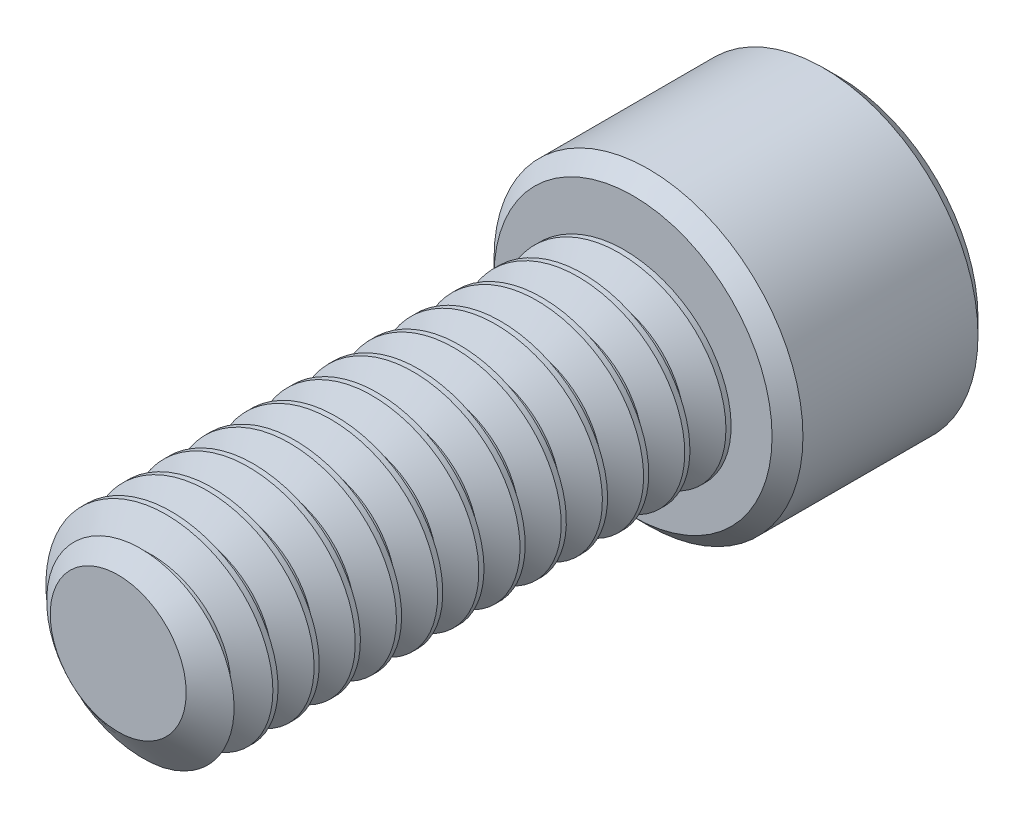
SolidWorks part; units mm, degrees
note: '?' marks a value the reader was unsure of.
other "DetailItem1"
ref_plane "Front Plane" through (0, 0, 0) normal (0, 0, 1) x (1, 0, 0)
ref_plane "Top Plane" through (0, 0, 0) normal (0, 1, 0) x (1, 0, 0)
ref_plane "Right Plane" through (0, 0, 0) normal (1, 0, 0) x (0, 0, -1)
sketch "Sketch1" plane through (0, 0, 0) normal (0, 0, 1) x (1, 0, 0)
  circle A0 centre (0, 0) radius 3.175
  dimension "OD" = 6.35
extrude "Extrude1" add sketch "Sketch1" against normal blind 15.875
sketch "Sketch2" plane through (0, 0, 0) normal (0, 0, 1) x (1, 0, 0)
  circle A0 centre (0, 0) radius 3.175 construction
  circle A1 centre (0, 0) radius 3.175
curve "Helix/Spiral1" pitch 1.27 height 17.145 turns 13.5 parameters "pitch"=1.27
sketch "Sketch3" plane through (0, 0, 0) normal (1, 0, 0) x (0, 0, -1)
  line L0 (-1.1112, 3.175) -> (-0.635, 2.3501)
  line L1 (-0.635, 2.3501) -> (-0.4762, 2.3501)
  line L2 (-0.4762, 2.3501) -> (0, 3.175)
  line L3 (-1.1112, 3.175) -> (0, 3.175)
  line L4 (-0.5556, 3.175) -> (-0.5556, 2.3501) construction
  line L5 (-0.8731, 2.7626) -> (-0.2381, 2.7626) construction
  line L6 (0, 3.175) -> (0, -3.175) construction
  dimension "D1" = 0.1588
  dimension "D2" = 0.635
  dimension "D3" = 60
sweep "Cut-Sweep1" cut profiles "Sketch3" path "Helix/Spiral1"
sketch "Sketch4" plane through (0, 0, 0) normal (1, 0, 0) x (0, 0, -1)
  line L0 (0.7554, 3.175) -> (0, 2.0961)
  line L1 (0, 2.0961) -> (0, 3.175)
  line L2 (0.7554, 3.175) -> (0, 3.175)
  line L3 (-1.1112, 3.175) -> (0, 3.175) construction
  line L4 (0, 0) -> (7.0209, 0) construction
  dimension "D1" = 55
  dimension "D2" = 0.254
revolve "Cut-Revolve1" cut sketch "Sketch4" angle 360 about L4
sketch "Sketch6" plane through (0, 0, -15.875) normal (0, 0, -1) x (-1, 0, 0)
  circle A0 centre (0, 0) radius 4.7625
  dimension "head dia" = 9.525
extrude "Extrude2" add sketch "Sketch6" along normal blind 6.35
sketch "Sketch7" plane through (0, 0, -22.225) normal (0, 0, -1) x (-1, 0, 0)
  line L1 (0, 2.7496) -> (-2.3812, 1.3748)
  line L2 (-2.3812, 1.3748) -> (-2.3813, -1.3748)
  line L3 (-2.3813, -1.3748) -> (0, -2.7496)
  line L4 (0, -2.7496) -> (2.3813, -1.3748)
  line L5 (2.3813, -1.3748) -> (2.3813, 1.3748)
  line L6 (2.3813, 1.3748) -> (0, 2.7496)
  circle A0 centre (0, 0) radius 2.3813 construction
  dimension "hex dia" = 4.7625
extrude "Cut-Extrude1" cut sketch "Sketch7" against normal blind 3.5719
sketch "Sketch8" plane through (0, 0, -22.225) normal (0, 0, -1) x (-1, 0, 0)
  circle A0 centre (0, 0) radius 2.7496
extrude "Cut-Extrude2" cut sketch "Sketch8" against normal through all draft 45
chamfer "Chamfer1" distance 0.4763 angle 45 2 edges at (-4.7625, 0, -22.225) (-4.7625, 0, -15.875)
sketch "Sketch10" plane through (0, 0, -15.875) normal (0, 0, 1) x (1, 0, 0)
  circle A1 centre (0, 0) radius 3.175
  circle A2 centre (0, 0) radius 3.175
  dimension "D1" = 0
ref_plane "Plane1" through (0, 0, -38.1) normal (0, 0, 1) x (1, 0, 0)
extrude "partial thread" [suppressed] add sketch "Sketch10" along normal up to surface (12.7 mm away) separate body
chamfer "Chamfer2" [suppressed] distance 0.127 angle 45
combine bodies "Combine1" [suppressed] operation type? add bodies to combine 107 108
sketch "Sketch9" plane through (0, 0, 0) normal (1, 0, 0) x (0, 0, -1)
  line L0 (0, 3.175) -> (0, -3.175) construction
  line L1 (3.175, 3.175) -> (3.175, -3.175) construction
  dimension "D1" = 3.175
equation "\"D3@Helix/Spiral1\" = \"screw length@Extrude1\"+\"pitch@Helix/Spiral1\""
equation "\"D1@Sketch3\" = \"pitch@Helix/Spiral1\"*.125"
equation "\"D2@Sketch3\" = \"pitch@Helix/Spiral1\"*.5"
equation "\"D1@Cut-Extrude1\" = \"hex dia@Sketch7\"*.75"
equation "\"D1@Chamfer1\" = \"head dia@Sketch6\"*.05"
equation "\"D1@Sketch9\" = \"pitch@Helix/Spiral1\"*2.5"
equation "\"D1@Chamfer2\"=\"OD@Sketch1\"*.02"
